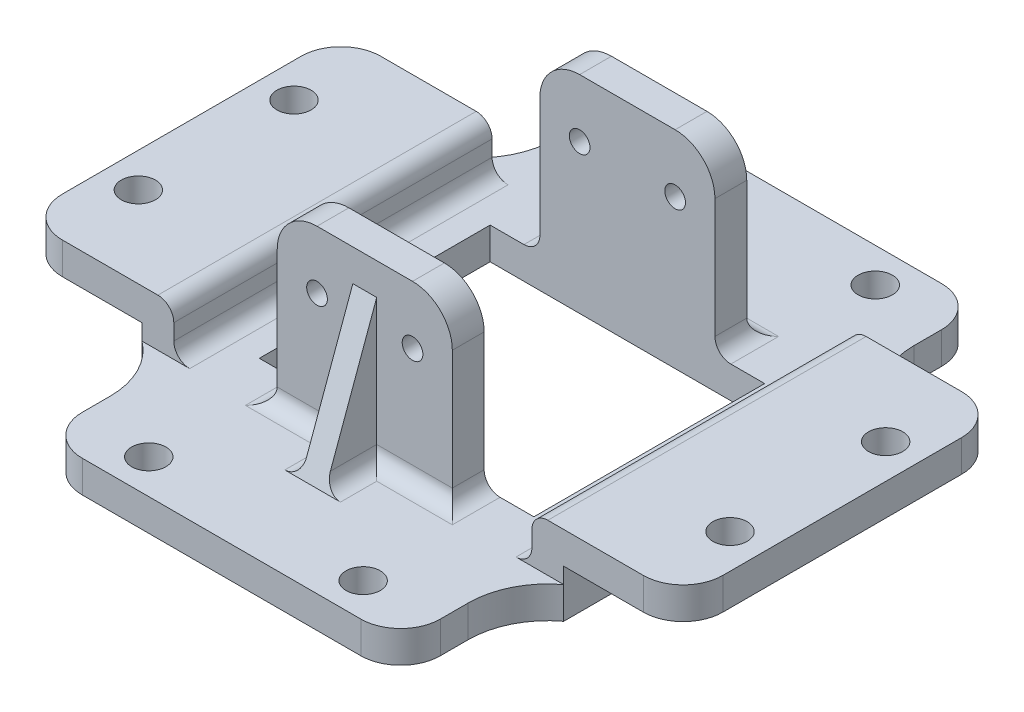
SolidWorks part; units mm, degrees
ref_plane "Front Plane" through (0, 0, 0) normal (0, 0, 1) x (1, 0, 0)
ref_plane "Top Plane" through (0, 0, 0) normal (0, 1, 0) x (1, 0, 0)
ref_plane "Right Plane" through (0, 0, 0) normal (1, 0, 0) x (0, 0, -1)
sketch "Sketch1" plane through (0, 0, 0) normal (0, 1, 0) x (1, 0, 0)
  line L1 (-17.25, 14.5) -> (17.25, 14.5)
  line L2 (-17.25, 14.5) -> (-17.25, -14.5)
  line L3 (-17.25, -14.5) -> (17.25, -14.5)
  line L4 (17.25, 14.5) -> (17.25, -14.5)
  line L5 (-17.25, 14.5) -> (17.25, -14.5) construction
  line L6 (-17.25, -14.5) -> (17.25, 14.5) construction
  line L7 (22.5, 36.5) -> (-22.5, 36.5)
  line L8 (22.5, 36.5) -> (22.5, -36.5)
  line L9 (22.5, -36.5) -> (-22.5, -36.5)
  line L10 (-22.5, 36.5) -> (-22.5, -36.5)
  line L11 (22.5, 36.5) -> (-22.5, -36.5) construction
  line L12 (22.5, -36.5) -> (-22.5, 36.5) construction
  point P0 (0, 0)
  point P6 (-20.688, -38.444)
  point P7 (0, 0)
  dimension "D1" = 29
  dimension "D2" = 34.5
  dimension "D3" = 73
  dimension "D4" = 45
extrude "Boss-Extrude1" add sketch "Sketch1" along normal blind 4
sketch "Sketch2" plane through (0, 0, 0) normal (0, 0, 1) x (1, 0, 0)
  line L0 (-22.5, 4) -> (-22.5, 10)
  line L1 (-22.5, 10) -> (-41.5, 10)
  line L2 (-41.5, 10) -> (-41.5, 6)
  line L3 (-41.5, 6) -> (-26.5, 6)
  line L4 (-26.5, 6) -> (-26.5, 0)
  line L5 (-26.5, 0) -> (-22.5, 0)
  line L6 (-22.5, 4) -> (-22.5, 0) construction
  line L7 (-22.5, 0) -> (22.5, 0) construction
  line L8 (-22.5, 0) -> (-22.5, 4)
  point P12 (-42.3323, 11.4402)
  point P13 (0, 0)
  point P14 (-41.3348, 10.9998)
  dimension "D1" = 4
  dimension "D2" = 19
  dimension "D3" = 6
extrude "Boss-Extrude2" add sketch "Sketch2" along normal mid plane 40
sketch "Sketch6" plane through (0, 4, 0) normal (0, 1, 0) x (1, 0, 0)
  line L0 (-17.25, -14.5) -> (17.25, -14.5) construction
  line L1 (-11, -14.5) -> (11, -14.5)
  line L2 (-11, -14.5) -> (-11, -18.5)
  line L3 (-11, -18.5) -> (11, -18.5)
  line L4 (11, -14.5) -> (11, -18.5)
  line L5 (0, -14.5) -> (0, 0) construction
  dimension "D1" = 22
  dimension "D2" = 4
extrude "Boss-Extrude3" add sketch "Sketch6" along normal blind 22
hole_wizard "#6 Clearance Hole1" positions "Sketch4" profile "Sketch5" hole size "#6" standard "ANSI Inch" end condition through all
sketch "Sketch4" plane through (0, 6, 0) normal (0, -1, 0) x (-1, 0, 0)
  arc A0 (37.175, -11.1316) -> (37.175, -8.4265) centre (37.175, -9.779) ccw construction
  arc A1 (37.175, 11.1316) -> (37.175, 8.4264) centre (37.175, 9.779) ccw construction
  point P0 (37.175, -9.779)
  point P2 (37.175, 9.779)
sketch "Sketch5" plane through (-37.175, 6, 9.779) normal (1, 0, 0) x (0, 0, -1)
  line L0 (0, 0) -> (0, 20)
  line L1 (0, 20) -> (2.1526, 20)
  line L2 (2.1526, 20) -> (2.1526, 0)
  line L5 (2.1526, 0) -> (0, 0)
  line L11 (0, -6.35) -> (0, 107.95) construction
  dimension "Thru Hole Dia." = 4.3053
  dimension "Thru Hole Depth" = 20
hole_wizard "#6 Clearance Hole2" positions "Sketch7" profile "Sketch8" hole size "#6" standard "ANSI Inch" end condition through all
sketch "Sketch7" plane through (0, 4, 0) normal (0, 1, 0) x (1, 0, 0)
  arc A0 (-14.8229, -32.175) -> (-12.1178, -32.175) centre (-13.4704, -32.175) ccw construction
  arc A1 (12.1178, -32.175) -> (14.8229, -32.175) centre (13.4704, -32.175) ccw construction
  point P0 (-13.4704, -32.175)
  point P2 (13.4704, -32.175)
  point P8 (0, 0)
sketch "Sketch8" plane through (-13.4704, 4, 32.175) normal (1, 0, 0) x (0, 0, 1)
  line L0 (0, 0) -> (0, 4)
  line L1 (0, 4) -> (2.1526, 4)
  line L2 (2.1526, 4) -> (2.1526, 0)
  line L5 (2.1526, 0) -> (0, 0)
  line L11 (0, -6.35) -> (0, 107.95) construction
  dimension "Thru Hole Dia." = 4.3053
  dimension "Thru Hole Depth" = 4
hole_wizard "M2 Clearance Hole1" positions "Sketch9" profile "Sketch10" hole size "M2" standard "ANSI Metric" end condition through all
sketch "Sketch9" plane through (0, 0, 18.5) normal (0, 0, 1) x (1, 0, 0)
  arc A0 (-7.05, 18.7) -> (-4.95, 18.7) centre (-6, 18.7) ccw construction
  arc A1 (4.95, 18.7) -> (7.05, 18.7) centre (6, 18.7) ccw construction
  point P0 (6, 18.7)
  point P2 (-6, 18.7)
sketch "Sketch10" plane through (6, 18.7, 18.5) normal (1, 0, 0) x (0, -1, 0)
  line L0 (0, 0) -> (0, 55)
  line L1 (0, 55) -> (1.3, 55)
  line L2 (1.3, 55) -> (1.3, 0)
  line L5 (1.3, 0) -> (0, 0)
  line L11 (0, -6.35) -> (0, 107.95) construction
  dimension "Thru Hole Dia." = 2.6
  dimension "Thru Hole Depth" = 55
sketch "Sketch12" plane through (0, 0, 0) normal (0, 0, 1) x (1, 0, 0)
  line L0 (-26.5, 0) -> (-41.5, 6)
rib "Rib3" sketch "Sketch12" sketch "Sketch12" thickness 3 extrusion direction parallel to sketch draft on no parameters "D1"=3
sketch "Sketch13" plane through (0, 0, 0) normal (1, 0, 0) x (0, 0, -1)
  line L0 (-25.0515, 4) -> (-18.5, 22)
  line L1 (-18.5, 26) -> (-18.5, 4) construction
  line L2 (-36.5, 4) -> (36.5, 4) construction
  line L3 (-18.5, 26) -> (-14.5, 26) construction
  dimension "D1" = 20
  dimension "D2" = 4
rib "Rib4" sketch "Sketch13" sketch "Sketch13" thickness 3 extrusion direction parallel to sketch draft on no parameters "D1"=3
mirror "Mirror1" about plane through (0, 0, 0) normal (0, 0, 1) of "#6 Clearance Hole2", "Boss-Extrude3", "M2 Clearance Hole1", "Rib4"
mirror "Mirror4" about plane through (0, 0, 0) normal (1, 0, 0) of "Rib3", "Boss-Extrude2", "#6 Clearance Hole1"
fillet "Fillet2" radius 2 16 edges at (-22.5, 4, 0) (-22.5, 10, 0) (11, 4, 16.5) (-6.25, 4, 18.5) (6.25, 4, 18.5) (-11, 4, 16.5) (11, 4, -16.5) (-11, 4, -16.5) (-6.25, 4, -18.5) (6.25, 4, -18.5) (22.5, 10, 0) (22.5, 4, 0) (-1.5, 4, -21.7757) (1.5, 4, -21.7757) (1.5, 4, 21.7757) (-1.5, 4, 21.7757)
fillet "Fillet3" radius 5 12 edges at (-41.5, 8, -20) (-41.5, 8, 20) (22.5, 2, -36.5) (-22.5, 2, -36.5) (22.5, 2, 36.5) (-22.5, 2, 36.5) (11, 26, 16.5) (-11, 26, 16.5) (41.5, 8, 20) (41.5, 8, -20) (-11, 26, -16.5) (11, 26, -16.5)
fillet "Fillet4" radius 10 4 edges at (22.5, 2, 20) (22.5, 2, -20) (-22.5, 2, -20) (-22.5, 2, 20)
